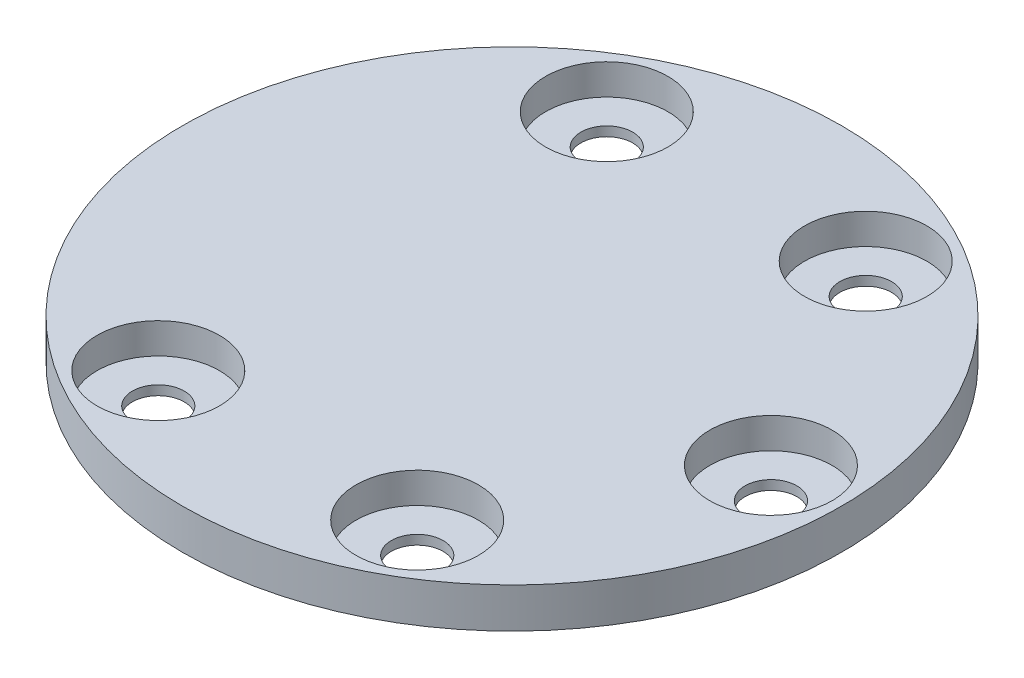
SolidWorks part; units mm, degrees
material "1060 Alloy"
ref_plane "Front Plane" through (0, 0, 0) normal (0, 0, 1) x (1, 0, 0)
ref_plane "Top Plane" through (0, 0, 0) normal (0, 1, 0) x (1, 0, 0)
ref_plane "Right Plane" through (0, 0, 0) normal (1, 0, 0) x (0, 0, -1)
sketch "Sketch1" plane through (0, 0, 0) normal (0, 1, 0) x (1, 0, 0)
  circle A0 centre (0, 0) radius 14
  dimension "D1" = 28
extrude "Boss-Extrude1" add sketch "Sketch1" along normal blind 1.7
sketch "Sketch3" plane through (0, 1.7, 0) normal (0, 1, 0) x (1, 0, 0)
  circle A0 centre (0, -10.25) radius 0.25
  circle A1 centre (0, 0) radius 9.8
  dimension "D1" = 0.5
  dimension "D2" = 10.25
  dimension "D3" = 19.6
sketch "Sketch4" plane through (0, 1.7, 0) normal (0, -1, 0) x (1, 0, 0)
  line L0 (0, 0) -> (13.2597, 13.2597) construction
  circle A0 centre (7.7782, 7.7782) radius 1
  dimension "D2" = 2
  dimension "D1" = 11
sketch "Sketch5" plane through (0, 1.7, 0) normal (0, 1, 0) x (1, 0, 0)
  circle A0 centre (0, 0) radius 11
  dimension "D1" = 22
hole_wizard "CBORE for M5 Hex Head Bolt1" positions "Sketch6" profile "Sketch7" counterbore size "M5" standard "ISO"
sketch "Sketch6" plane through (0, 1.7, 0) normal (0, 1, 0) x (1, 0, 0)
  point P0 (11, 0)
  dimension "D1" = 11
sketch "Sketch7" plane through (11, 1.7, 0) normal (1, 0, 0) x (0, 0, 1)
  line L0 (0, 0) -> (0, 5.6609)
  line L1 (0, 5.6609) -> (1.1, 5)
  line L2 (1.1, 5) -> (1.1, 1.3)
  line L3 (1.1, 1.3) -> (2.6, 1.3)
  line L4 (2.6, 1.3) -> (2.6, 0)
  line L5 (2.6, 0) -> (0, 0)
  line L10 (0, 5.6609) -> (-1.1, 5) construction
  line L11 (0, -6.35) -> (0, 107.95) construction
  dimension "Hole Dia." = 2.2
  dimension "Hole Depth" = 5
  dimension "C'Bore Dia." = 5.2
  dimension "C'Bore Depth" = 1.3
  dimension "Drill Angle" = 118
pattern_circular "CirPattern1" count 6 over 360 about axis through (0, 1.7, 0) along (0, 1, 0) skipping 3 of "CBORE for M5 Hex Head Bolt1"
sketch "Sketch8" plane through (0, 0, 0) normal (0, -1, 0) x (1, 0, 0)
  line L1 (3.1, 0.4) -> (4.9, 0.4)
  line L2 (3.1, 0.4) -> (3.1, -0.4)
  line L3 (3.1, -0.4) -> (4.9, -0.4)
  line L4 (4.9, 0.4) -> (4.9, -0.4)
  dimension "D1" = 1.8
  dimension "D2" = 0.8
  dimension "D3" = 0.4
  dimension "D4" = 3.1
extrude "Boss-Extrude2" add sketch "Sketch8" along normal blind 1
fillet "Fillet1" radius 0.25 12 edges at (3.1, 0, 0) (4.9, 0, 0) (4.9, -0.5, 0.4) (3.1, -0.5, 0.4) (4, 0, 0.4) (3.1, -0.5, -0.4) (4.9, -0.5, -0.4) (4, 0, -0.4) (4, -1, 0.4) (4.9, -1, 0) (4, -1, -0.4) (3.1, -1, 0)
